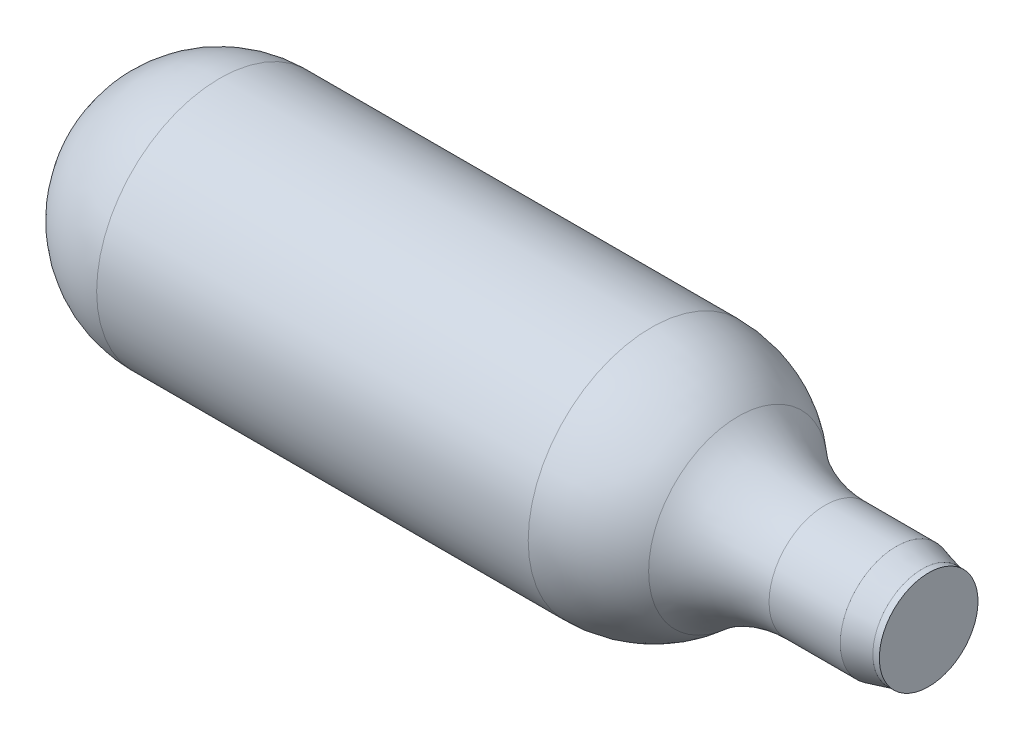
SolidWorks part; units mm, degrees
material "AISI 304"
ref_plane "Front Plane" through (0, 0, 0) normal (0, 0, 1) x (1, 0, 0)
ref_plane "Top Plane" through (0, 0, 0) normal (0, 1, 0) x (1, 0, 0)
ref_plane "Right Plane" through (0, 0, 0) normal (1, 0, 0) x (0, 0, -1)
sketch "Sketch1" plane through (0, 0, 0) normal (0, 0, 1) x (1, 0, 0)
  line L0 (0, 0) -> (64.25, 0)
  line L1 (9.5, 9.5) -> (42.8254, 9.5)
  line L2 (71.9039, 0) -> (83.8195, 0) construction
  line L3 (56.25, 4.325) -> (64.25, 4.325)
  line L4 (64.25, 4.325) -> (64.25, 0)
  arc A0 (0, 0) -> (9.5, 9.5) centre (9.5, 0) cw
  arc A1 (42.8254, 9.5) -> (49.5377, 6.9125) centre (42.8254, -0.5) cw
  arc A2 (49.5377, 6.9125) -> (56.25, 4.325) centre (56.25, 14.325) ccw
  dimension "D4" = 10
  dimension "D1" = 64.25
  dimension "D2" = 19
  dimension "D3" = 8.65
  dimension "D5" = 8
revolve "Revolve1" add sketch "Sketch1" angle 360 about L2
sketch "Sketch2" plane through (64.25, 0, 0) normal (1, 0, 0) x (0, 0, -1)
  circle A0 centre (0, 0) radius 3.81
  dimension "D1" = 7.62
extrude "Cut-Extrude1" cut sketch "Sketch2" against normal blind 0.5 flip side to cut
chamfer "Chamfer1" distance 2 distance2 0.515 1 edges at (63.75, 0, -4.325) first distance on face at (56.25, 0, 4.325)
